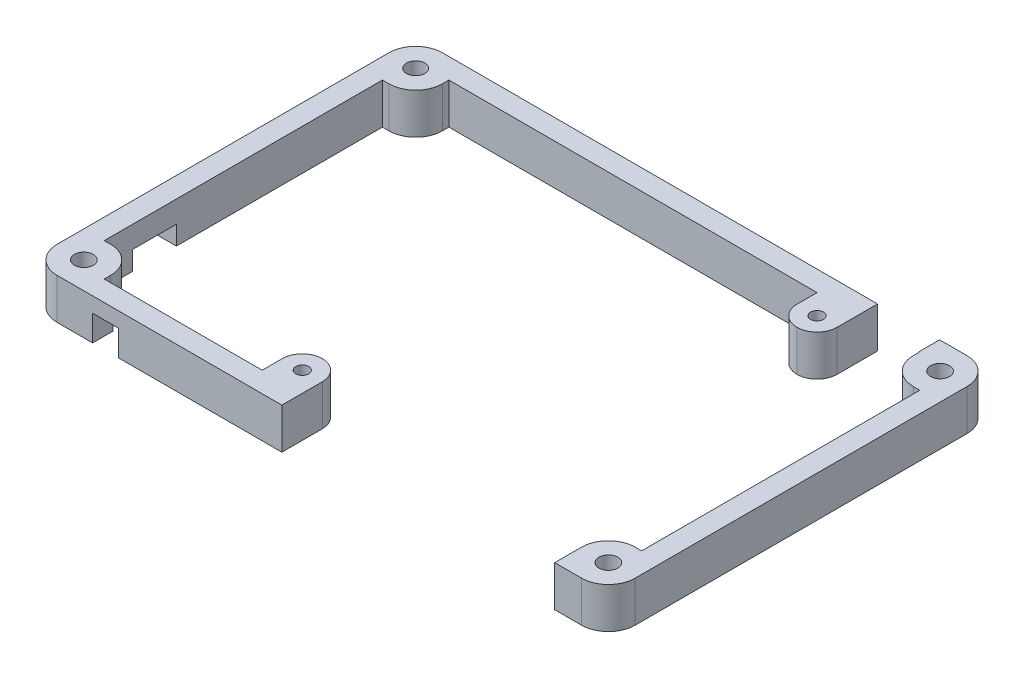
SolidWorks part; units mm, degrees
material "Rubber"
ref_plane "Front" through (0, 0, 0) normal (0, 0, 1) x (1, 0, 0)
ref_plane "Top" through (0, 0, 0) normal (0, 1, 0) x (1, 0, 0)
ref_plane "Right" through (0, 0, 0) normal (1, 0, 0) x (0, 0, -1)
sketch "Sketch1" plane through (0, 0, 0) normal (0, 1, 0) x (1, 0, 0)
  line L0 (-45, 0) -> (45, 0) construction
  line L1 (-45, 30) -> (45, 30) construction
  line L2 (-45, 30) -> (-45, -30) construction
  line L3 (-45, -30) -> (45, -30) construction
  line L4 (45, 30) -> (45, -30) construction
  line L5 (0, -30) -> (0, 30) construction
  line L6 (41.825, 26.825) -> (41.825, -26.825) construction
  line L7 (-41.825, -26.825) -> (41.825, -26.825) construction
  line L8 (-41.825, 26.825) -> (-41.825, -26.825) construction
  line L9 (-41.825, 26.825) -> (41.825, 26.825) construction
  line L10 (40.825, 25.825) -> (40.825, -25.825) construction
  line L11 (-40.825, -25.825) -> (40.825, -25.825) construction
  line L12 (-40.825, 25.825) -> (-40.825, -25.825) construction
  line L13 (-40.825, 25.825) -> (40.825, 25.825) construction
  line L14 (40.825, 21.65) -> (45, 21.65) construction
  line L15 (40.825, -21.65) -> (45, -21.65) construction
  line L16 (36.65, -25.825) -> (36.65, -30) construction
  line L17 (-36.65, -25.825) -> (-36.65, -30) construction
  line L18 (-40.825, -21.65) -> (-45, -21.65) construction
  line L19 (-36.65, 25.825) -> (-36.65, 30) construction
  line L20 (-40.825, 21.65) -> (-45, 21.65) construction
  line L21 (36.65, 25.825) -> (36.65, 30) construction
  line L22 (40.825, -25.825) -> (41.825, -25.825) construction
  circle A0 centre (-40.825, -25.825) radius 1 construction
  circle A1 centre (40.825, -25.825) radius 1 construction
  circle A2 centre (40.825, 25.825) radius 1 construction
  circle A3 centre (-40.825, 25.825) radius 1 construction
  circle A4 centre (40.825, -25.825) radius 4.175 construction
  circle A5 centre (40.825, 25.825) radius 4.175 construction
  circle A6 centre (-40.825, 25.825) radius 4.175 construction
  circle A7 centre (-40.825, -25.825) radius 4.175 construction
  dimension "D1" = 90
  dimension "D2" = 60
  dimension "D4" = 1
  dimension "D3" = 3.175
sketch "Sketch2" plane through (0, 0, 0) normal (0, 1, 0) x (1, 0, 0)
  line L0 (-45, 30) -> (-45, -30) construction
  line L1 (-45, -30) -> (45, -30) construction
  line L2 (45, 30) -> (45, -30) construction
  line L3 (-45, 30) -> (45, 30) construction
  line L4 (40.825, 21.65) -> (45, 21.65) construction
  line L5 (36.65, 25.825) -> (36.65, 30) construction
  line L6 (-36.65, 25.825) -> (-36.65, 30) construction
  line L7 (-40.825, 21.65) -> (-45, 21.65) construction
  line L8 (-36.65, -25.825) -> (-36.65, -30) construction
  line L9 (-40.825, -21.65) -> (-45, -21.65) construction
  line L10 (36.65, -25.825) -> (36.65, -30) construction
  line L11 (40.825, -21.65) -> (45, -21.65) construction
  line L16 (-45, 25.825) -> (-45, -25.825)
  line L17 (-40.825, -30) -> (40.825, -30)
  line L18 (45, 25.825) -> (45, -25.825)
  line L19 (-40.825, 30) -> (40.825, 30)
  line L20 (40.825, 21.65) -> (41.825, 21.65)
  line L21 (36.65, 25.825) -> (36.65, 26.825)
  line L22 (-36.65, 25.825) -> (-36.65, 26.825)
  line L23 (-40.825, 21.65) -> (-41.825, 21.65)
  line L24 (-36.65, -25.825) -> (-36.65, -26.825)
  line L25 (-40.825, -21.65) -> (-41.825, -21.65)
  line L26 (36.65, -25.825) -> (36.65, -26.825)
  line L27 (40.825, -21.65) -> (41.825, -21.65)
  line L28 (41.825, 26.825) -> (41.825, -26.825) construction
  line L29 (-36.65, -26.825) -> (36.65, -26.825)
  line L30 (-41.825, 26.825) -> (41.825, 26.825) construction
  line L31 (-41.825, 26.825) -> (-41.825, -26.825) construction
  line L32 (-36.65, 26.825) -> (36.65, 26.825)
  line L33 (-41.825, 21.65) -> (-41.825, -21.65)
  line L34 (41.825, 21.65) -> (41.825, -21.65)
  line L35 (-41.825, -26.825) -> (41.825, -26.825) construction
  circle A0 centre (40.825, 25.825) radius 4.175 construction
  circle A1 centre (40.825, 25.825) radius 1 construction
  circle A2 centre (-40.825, 25.825) radius 4.175 construction
  circle A3 centre (-40.825, 25.825) radius 1 construction
  circle A4 centre (-40.825, -25.825) radius 4.175 construction
  circle A5 centre (40.825, -25.825) radius 4.175 construction
  arc A6 (45, 25.825) -> (40.825, 30) centre (40.825, 25.825) ccw
  circle A7 centre (40.825, 25.825) radius 1 construction
  arc A8 (-40.825, 30) -> (-45, 25.825) centre (-40.825, 25.825) ccw
  circle A9 centre (-40.825, 25.825) radius 1 construction
  arc A10 (-36.65, -25.825) -> (-40.825, -21.65) centre (-40.825, -25.825) ccw
  arc A11 (40.825, -21.65) -> (36.65, -25.825) centre (40.825, -25.825) ccw
  circle A12 centre (-40.825, -25.825) radius 1 construction
  circle A13 centre (40.825, -25.825) radius 1 construction
  circle A14 centre (-40.825, -25.825) radius 1 construction
  circle A15 centre (40.825, -25.825) radius 1 construction
  arc A16 (-40.825, 21.65) -> (-36.65, 25.825) centre (-40.825, 25.825) ccw
  arc A17 (-45, -25.825) -> (-40.825, -30) centre (-40.825, -25.825) ccw
  arc A18 (40.825, -30) -> (45, -25.825) centre (40.825, -25.825) ccw
  arc A19 (36.65, 25.825) -> (40.825, 21.65) centre (40.825, 25.825) ccw
extrude "Boss-Extrude3" add sketch "Sketch2" along normal blind 6.35
sketch "Sketch3" plane through (0, 0, -30) normal (0, 0, -1) x (-1, 0, 0)
  line L0 (-40.825, 6.35) -> (40.825, 6.35) construction
  line L1 (-36.566, 6.35) -> (-26.9027, 6.35)
  line L2 (-36.566, 6.35) -> (-36.566, 0)
  line L3 (-36.566, 0) -> (-26.9027, 0)
  line L4 (-26.9027, 6.35) -> (-26.9027, 0)
  line L5 (-40.825, 0) -> (40.825, 0) construction
extrude "Cut-Extrude1" cut sketch "Sketch3" against normal up to vertex (3.175 mm away) up to point (36.65, 6.35, -26.825)
sketch "Sketch4" plane through (0, 0, 30) normal (0, 0, 1) x (1, 0, 0)
  line L0 (-40.825, 6.35) -> (40.825, 6.35) construction
  line L1 (36.65, 6.35) -> (-5.825, 6.35)
  line L2 (36.65, 6.35) -> (36.65, 0)
  line L3 (36.65, 0) -> (-5.825, 0)
  line L4 (-5.825, 6.35) -> (-5.825, 0)
  line L5 (-40.825, 0) -> (40.825, 0) construction
  line L6 (-40.825, 6.35) -> (-40.825, 0) construction
  dimension "D1" = 35
extrude "Cut-Extrude2" cut sketch "Sketch4" against normal up to vertex (3.175 mm away) up to point (36.65, 6.35, 26.825)
sketch "Sketch5" plane through (-45, 0, 0) normal (-1, 0, 0) x (0, 0, 1)
  line L0 (13.825, 0) -> (25.825, 0) construction
  line L1 (25.825, 6.35) -> (25.825, 0) construction
  line L3 (17.225, 2.95) -> (10.425, 2.95)
  line L4 (17.225, 2.95) -> (17.225, -2.95)
  line L5 (17.225, -2.95) -> (10.425, -2.95)
  line L6 (10.425, 2.95) -> (10.425, -2.95)
  line L7 (17.225, 2.95) -> (10.425, -2.95) construction
  line L8 (17.225, -2.95) -> (10.425, 2.95) construction
  dimension "D1" = 12
  dimension "D2" = 6.8
  dimension "D3" = 5.9
extrude "Cut-Extrude3" cut sketch "Sketch5" against normal up to surface (3.175 mm away) up to face at (-41.825, 3.175, 0)
sketch "Sketch6" plane through (0, 0, 0) normal (0, -1, 0) x (1, 0, 0)
  circle A0 centre (40.825, 25.825) radius 1.4732
  circle A1 centre (40.825, -25.8149) radius 1.4732
  dimension "D1" = 2.9464
  dimension "D2" = 2.9464
extrude "Cut-Extrude4" cut sketch "Sketch6" against normal up to surface (6.35 mm away) up to face at (39.763, 6.35, -3.8321)
sketch "Sketch7" plane through (0, 0, 0) normal (0, -1, 0) x (1, 0, 0)
  circle A0 centre (-40.825, -25.825) radius 1.4224
  circle A1 centre (-40.825, 25.825) radius 1.4732
  circle A2 centre (-40.825, 25.825) radius 1 construction
  dimension "D1" = 2.8448
  dimension "D2" = 2.9464
extrude "Cut-Extrude5" cut sketch "Sketch7" against normal up to surface (6.35 mm away) up to face at (-27.5872, 6.35, 0)
sketch "Sketch8" plane through (0, 0, 26.825) normal (0, 0, -1) x (-1, 0, 0)
  line L0 (36.65, 0) -> (5.825, 0) construction
  line L1 (5.825, 6.35) -> (12.065, 6.35)
  line L2 (5.825, 6.35) -> (5.825, 0)
  line L3 (5.825, 0) -> (12.065, 0)
  line L4 (12.065, 6.35) -> (12.065, 0)
  dimension "D1" = 6.24
extrude "Boss-Extrude4" add sketch "Sketch8" along normal blind 6.24
sketch "Sketch9" plane through (0, 0, -26.825) normal (0, 0, 1) x (1, 0, 0)
  line L0 (26.9027, 0) -> (-36.65, 0) construction
  line L1 (26.9027, 6.35) -> (20.6627, 6.35)
  line L2 (26.9027, 6.35) -> (26.9027, 0)
  line L3 (26.9027, 0) -> (20.6627, 0)
  line L4 (20.6627, 6.35) -> (20.6627, 0)
  dimension "D1" = 6.24
extrude "Boss-Extrude5" add sketch "Sketch9" along normal blind 6.24
sketch "Sketch10" plane through (0, 0, 0) normal (0, -1, 0) x (-1, 0, 0)
  line L0 (-20.6627, 26.825) -> (-26.9027, 20.585) construction
  line L1 (12.065, -26.825) -> (5.825, -20.585) construction
  circle A0 centre (-23.7827, 23.705) radius 1
  circle A1 centre (8.945, -23.705) radius 1
extrude "Cut-Extrude6" cut sketch "Sketch10" against normal through all
fillet "Fillet1" radius 3.12 4 edges at (-12.065, 3.175, 20.585) (-5.825, 3.175, 20.585) (26.9027, 3.175, -20.585) (20.6627, 3.175, -20.585)
sketch "Sketch11" plane through (0, 0, 30) normal (0, 0, 1) x (1, 0, 0)
  line L0 (-40.825, 0) -> (-5.825, 0) construction
  line L1 (-35.285, 4) -> (-31.285, 4)
  line L2 (-35.285, 4) -> (-35.285, 0)
  line L3 (-35.285, 0) -> (-31.285, 0)
  line L4 (-31.285, 4) -> (-31.285, 0)
  line L5 (-35.285, 4) -> (-31.285, 0) construction
  line L6 (-35.285, 0) -> (-31.285, 4) construction
  line L7 (-40.825, 6.35) -> (-40.825, 0) construction
  point P0 (-33.285, 2)
  dimension "D1" = 4
  dimension "D2" = 4
  dimension "D3" = 5.54
extrude "Cut-Extrude7" cut sketch "Sketch11" against normal blind 10
